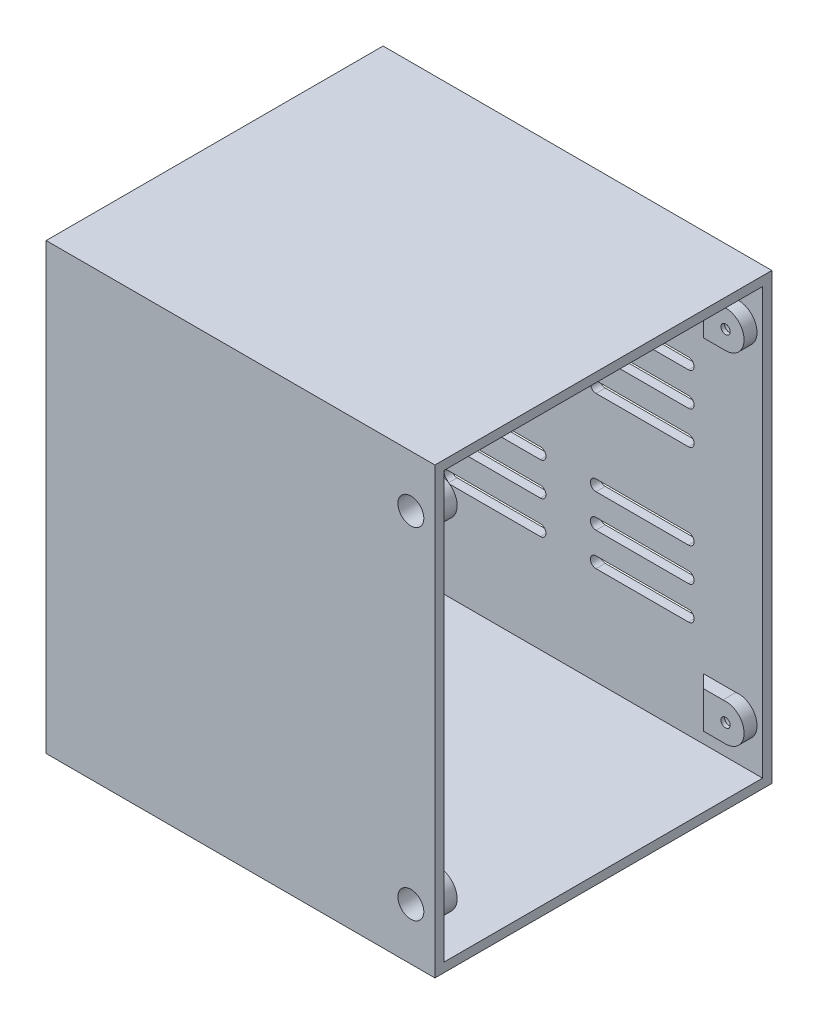
SolidWorks part; units mm, degrees
ref_plane "Front Plane" through (0, 0, 0) normal (0, 0, 1) x (1, 0, 0)
ref_plane "Top Plane" through (0, 0, 0) normal (0, 1, 0) x (1, 0, 0)
ref_plane "Right Plane" through (0, 0, 0) normal (1, 0, 0) x (0, 0, -1)
sketch "Sketch1" plane through (205.5525, 0, 0) normal (1, 0, 0) x (0, 0, -1)
  line L0 (1.5129, 48.8646) -> (1.513, -71.1354) construction
  line L1 (-89.4871, 48.8644) -> (1.5129, 48.8646) construction
  line L2 (-89.4871, 48.8644) -> (-89.487, -71.1356) construction
  line L3 (-89.487, -71.1356) -> (1.513, -71.1354) construction
  line L4 (1.5129, 48.8646) -> (1.513, -71.1354)
  line L5 (-89.4871, 48.8644) -> (1.5129, 48.8646)
  line L6 (-89.4871, 48.8644) -> (-89.487, -71.1356)
  line L7 (-89.487, -71.1356) -> (1.513, -71.1354)
  line L8 (-86.987, -68.6356) -> (-0.987, -68.6355)
  line L9 (-0.9871, 46.3645) -> (-0.987, -68.6355)
  line L10 (-86.9871, 46.3644) -> (-0.9871, 46.3645)
  line L11 (-86.9871, 46.3644) -> (-86.987, -68.6356)
  dimension "D1" = 2.5
extrude "Boss-Extrude1" add sketch "Sketch1" along normal up to surface (105 mm away)
sketch "Sketch2" plane through (0, 0, 86.9871) normal (0, 0, -1) x (-1, 0, 0)
  line L0 (-205.5525, 46.3645) -> (-205.5525, -68.6355) construction
  line L1 (-208.4525, -46.1353) -> (-206.5525, -46.1353)
  line L2 (-208.4525, -46.1353) -> (-208.4525, -40.1355)
  line L3 (-208.4525, -40.1355) -> (-206.5525, -40.1355)
  line L4 (-206.5525, -46.1353) -> (-206.5525, -40.1355)
  line L5 (-206.5525, 23.8645) -> (-208.4525, 23.8645)
  line L6 (-206.5525, 23.8645) -> (-206.5525, 17.8647)
  line L7 (-206.5525, 17.8647) -> (-208.4525, 17.8647)
  line L8 (-208.4525, 23.8645) -> (-208.4525, 17.8647)
  dimension "D1" = 0.1
  dimension "D2" = 1
  dimension "D3" = 0.1
  dimension "D4" = 1
  dimension "D5" = 0
  dimension "D6" = 0
  dimension "D7" = 0
  dimension "D8" = 0
extrude "Boss-Extrude2" add sketch "Sketch2" along normal offset from surface (1.3 mm away) 0.2
sketch "Sketch3" plane through (0, 0, 0.9871) normal (0, 0, 1) x (1, 0, 0)
  line L1 (210.0525, 28.8645) -> (225.0525, 28.8645)
  line L2 (210.0525, 28.8645) -> (210.0525, -51.1355)
  line L3 (210.0525, -51.1355) -> (225.0525, -51.1355)
  line L4 (225.0525, 28.8645) -> (225.0525, -51.1355)
  line L6 (205.5525, -68.6355) -> (205.5525, 46.3645) construction
  line L7 (310.5525, -71.1355) -> (205.5525, -71.1355) construction
  line L8 (310.5525, 48.8645) -> (205.5525, 48.8645) construction
  dimension "D1" = 4.5
  dimension "D2" = 15
  dimension "D3" = 20
  dimension "D4" = 20
extrude "Cut-Extrude1" cut sketch "Sketch3" against normal blind 0.5
sketch "Sketch4" plane through (0, 0, 0.9871) normal (0, 0, 1) x (1, 0, 0)
  line L0 (212.0525, 39.8645) -> (205.5525, 39.8645)
  line L1 (205.5525, -68.6355) -> (205.5525, 46.3645) construction
  line L2 (212.0525, 29.8645) -> (205.5525, 29.8645)
  line L3 (205.5525, 29.8645) -> (205.5525, 39.8645)
  line L4 (212.0525, -52.1355) -> (205.5525, -52.1355)
  line L5 (212.0525, -62.1355) -> (205.5525, -62.1355)
  line L6 (205.5525, -62.1355) -> (205.5525, -52.1355)
  line L7 (304.0525, -62.1355) -> (294.0525, -62.1355)
  line L8 (294.0525, -62.1355) -> (294.0525, -52.1855)
  line L9 (304.1025, -52.1855) -> (294.0525, -52.1855)
  line L10 (304.0525, 29.8645) -> (294.0525, 29.8645)
  line L11 (304.0525, 39.8645) -> (294.0525, 39.8645)
  line L12 (294.0525, 39.8645) -> (294.0525, 29.8645)
  circle A0 centre (212.0525, 34.8645) radius 2.25 construction
  circle A1 centre (212.0525, -57.1355) radius 2.25 construction
  circle A2 centre (212.0525, 34.8645) radius 2.25 construction
  circle A3 centre (212.0525, -57.1355) radius 2.25 construction
  circle A4 centre (212.0525, -57.1355) radius 5
  circle A5 centre (212.0525, 34.8645) radius 5
  circle A6 centre (212.0525, -57.1355) radius 3.5
  circle A7 centre (212.0525, 34.8645) radius 3.5
  circle A8 centre (212.0525, 34.8645) radius 1.25
  circle A9 centre (212.0525, -57.1355) radius 1.25
  circle A10 centre (304.0525, 34.8645) radius 1.6 construction
  circle A11 centre (304.0525, -57.1355) radius 1.6 construction
  circle A12 centre (304.0525, 34.8645) radius 1.6 construction
  circle A13 centre (304.0525, -57.1355) radius 1.6 construction
  circle A14 centre (304.0525, 34.8645) radius 5
  circle A15 centre (304.0525, -57.1355) radius 5
  circle A16 centre (304.0525, -57.1355) radius 3.5
  circle A17 centre (304.0525, -57.1355) radius 1.25
  circle A18 centre (304.0525, 34.8645) radius 3.5
  circle A19 centre (304.0525, 34.8645) radius 1.25
  line M7 (205.5525, 46.3645) -> (205.5525, -68.6355)
  dimension "D1" = 10
  dimension "D2" = 10
  dimension "D3" = 7
  dimension "D4" = 7
  dimension "D5" = 2.5
  dimension "D6" = 2.5
  dimension "D7" = 10
  dimension "D8" = 7
  dimension "D9" = 2.5
  dimension "D10" = 10
  dimension "D11" = 7
  dimension "D12" = 2.5
  dimension "D13" = 10
  dimension "D14" = 10
extrude "Boss-Extrude3" add sketch "Sketch4" along normal up to surface (3.5 mm away) contours A5 A7 | A4 A6 | A5 L0 L2 M7 | A4 L4 L5 M7 | A15 A16 | A14 A18 | A14 L11 L12 L10 | A15 L9 L8 L7 region at (206.9332, 34.8645, 0.9871) region at (208.8025, -52.2547, 0.9871) region at (215.488, 38.3001, 0.9871) region at (215.488, -53.6999, 0.9871) region at (299.2061, -57.479, 0.9871) region at (297.1787, -57.1748, 0.9871) region at (297.1915, 34.8645, 0.9871) region at (299.1939, 34.8645, 0.9871)
extrude "Boss-Extrude4" add sketch "Sketch4<3>" against normal blind 1 from surface contours A7 A8 | A18 A19 | A16 A17 | A6 A9 region at (208.6515, -57.1355, 0.9871) region at (208.6515, 34.8645, 0.9871) region at (300.6515, -57.1355, 0.9871) region at (300.6515, 34.8645, 0.9871) starting at face at (307.5525, 34.8645, 4.4871)
sketch "Sketch4<3>" plane through (0, 0, 0.9871) normal (0, 0, 1) x (1, 0, 0) same geometry as "Sketch4"
extrude "Cut-Extrude2" cut sketch "Sketch4<4>" against normal through all contours A6 A9 | A9 | A7 A8 | A8 | A17 | A16 A17 | A19 | A18 A19 region at (208.6515, -57.1355, 0.9871) region at (208.6515, 34.8645, 0.9871) region at (212.0525, 34.8645, 0.9871) region at (212.0525, -57.1355, 0.9871) region at (300.6515, -57.1355, 0.9871) region at (304.0525, -57.1355, 0.9871) region at (300.6515, 34.8645, 0.9871) region at (304.0525, 34.8645, 0.9871)
sketch "Sketch4<4>" plane through (0, 0, 0.9871) normal (0, 0, 1) x (1, 0, 0) same geometry as "Sketch4"
chamfer "Chamfer1" distance 4 angle 45 1 edges at (294.0525, -57.1605, 4.4871)
chamfer "Chamfer2" distance 4 angle 45 1 edges at (294.0525, 34.8645, 4.4871)
sketch "Sketch5" plane through (0, 0, -1.5129) normal (0, 0, -1) x (-1, 0, 0)
  line L0 (-258.0525, 48.8645) -> (-258.0525, -71.1355) construction
  line L1 (-310.5525, 48.8645) -> (-205.5525, 48.8645) construction
  line L2 (-310.5525, -71.1355) -> (-205.5525, -71.1355) construction
  line L3 (-310.5525, -11.1355) -> (-205.5525, -11.1355) construction
  line L4 (-310.5525, -71.1355) -> (-310.5525, 48.8645) construction
  line L5 (-205.5525, 48.8645) -> (-205.5525, -71.1355) construction
  line L6 (-290.5525, 10.8645) -> (-290.5525, 7.8645)
  line L7 (-290.5525, 1.8645) -> (-265.5525, 1.8645)
  line L8 (-290.5525, 1.8645) -> (-290.5525, -1.1355)
  line L9 (-290.5525, -1.1355) -> (-265.5525, -1.1355)
  line L10 (-265.5525, 1.8645) -> (-265.5525, -1.1355)
  line L11 (-290.5525, 10.8645) -> (-265.5525, 10.8645)
  line L12 (-265.5525, 10.8645) -> (-265.5525, 7.8645)
  line L13 (-290.5525, 7.8645) -> (-265.5525, 7.8645)
  line L14 (-290.5525, 19.8645) -> (-290.5525, 16.8645)
  line L15 (-290.5525, 19.8645) -> (-265.5525, 19.8645)
  line L16 (-265.5525, 19.8645) -> (-265.5525, 16.8645)
  line L17 (-290.5525, 16.8645) -> (-265.5525, 16.8645)
  line L18 (-225.5525, 16.8645) -> (-250.5525, 16.8645)
  line L19 (-250.5525, 19.8645) -> (-250.5525, 16.8645)
  line L20 (-225.5525, 19.8645) -> (-250.5525, 19.8645)
  line L21 (-225.5525, 19.8645) -> (-225.5525, 16.8645)
  line L22 (-225.5525, 7.8645) -> (-250.5525, 7.8645)
  line L23 (-250.5525, 10.8645) -> (-250.5525, 7.8645)
  line L24 (-225.5525, 10.8645) -> (-250.5525, 10.8645)
  line L25 (-250.5525, 1.8645) -> (-250.5525, -1.1355)
  line L26 (-225.5525, -1.1355) -> (-250.5525, -1.1355)
  line L27 (-225.5525, 1.8645) -> (-225.5525, -1.1355)
  line L28 (-225.5525, 1.8645) -> (-250.5525, 1.8645)
  line L29 (-225.5525, 10.8645) -> (-225.5525, 7.8645)
  line L30 (-225.5525, -33.1355) -> (-225.5525, -30.1355)
  line L31 (-225.5525, -24.1355) -> (-250.5525, -24.1355)
  line L32 (-225.5525, -24.1355) -> (-225.5525, -21.1355)
  line L33 (-225.5525, -21.1355) -> (-250.5525, -21.1355)
  line L34 (-250.5525, -24.1355) -> (-250.5525, -21.1355)
  line L35 (-225.5525, -33.1355) -> (-250.5525, -33.1355)
  line L36 (-250.5525, -33.1355) -> (-250.5525, -30.1355)
  line L37 (-225.5525, -30.1355) -> (-250.5525, -30.1355)
  line L38 (-225.5525, -42.1355) -> (-225.5525, -39.1355)
  line L39 (-225.5525, -42.1355) -> (-250.5525, -42.1355)
  line L40 (-250.5525, -42.1355) -> (-250.5525, -39.1355)
  line L41 (-225.5525, -39.1355) -> (-250.5525, -39.1355)
  line L42 (-290.5525, -39.1355) -> (-265.5525, -39.1355)
  line L43 (-265.5525, -42.1355) -> (-265.5525, -39.1355)
  line L44 (-290.5525, -42.1355) -> (-265.5525, -42.1355)
  line L45 (-290.5525, -42.1355) -> (-290.5525, -39.1355)
  line L46 (-290.5525, -30.1355) -> (-265.5525, -30.1355)
  line L47 (-265.5525, -33.1355) -> (-265.5525, -30.1355)
  line L48 (-290.5525, -33.1355) -> (-265.5525, -33.1355)
  line L49 (-265.5525, -24.1355) -> (-265.5525, -21.1355)
  line L50 (-290.5525, -21.1355) -> (-265.5525, -21.1355)
  line L51 (-290.5525, -24.1355) -> (-290.5525, -21.1355)
  line L52 (-290.5525, -24.1355) -> (-265.5525, -24.1355)
  line L53 (-290.5525, -33.1355) -> (-290.5525, -30.1355)
  arc A0 (-265.5525, 1.8645) -> (-265.5525, -1.1355) centre (-265.5525, 0.3645) cw
  arc A1 (-290.5525, -1.1355) -> (-290.5525, 1.8645) centre (-290.5525, 0.3645) cw
  arc A2 (-265.5525, 10.8645) -> (-265.5525, 7.8645) centre (-265.5525, 9.3645) cw
  arc A3 (-290.5525, 7.8645) -> (-290.5525, 10.8645) centre (-290.5525, 9.3645) cw
  arc A4 (-265.5525, 19.8645) -> (-265.5525, 16.8645) centre (-265.5525, 18.3645) cw
  arc A5 (-290.5525, 16.8645) -> (-290.5525, 19.8645) centre (-290.5525, 18.3645) cw
  arc A6 (-225.5525, 16.8645) -> (-225.5525, 19.8645) centre (-225.5525, 18.3645) ccw
  arc A7 (-250.5525, 19.8645) -> (-250.5525, 16.8645) centre (-250.5525, 18.3645) ccw
  arc A8 (-225.5525, 7.8645) -> (-225.5525, 10.8645) centre (-225.5525, 9.3645) ccw
  arc A9 (-250.5525, 10.8645) -> (-250.5525, 7.8645) centre (-250.5525, 9.3645) ccw
  arc A10 (-225.5525, -1.1355) -> (-225.5525, 1.8645) centre (-225.5525, 0.3645) ccw
  arc A11 (-250.5525, 1.8645) -> (-250.5525, -1.1355) centre (-250.5525, 0.3645) ccw
  arc A12 (-250.5525, -24.1355) -> (-250.5525, -21.1355) centre (-250.5525, -22.6355) cw
  arc A13 (-225.5525, -21.1355) -> (-225.5525, -24.1355) centre (-225.5525, -22.6355) cw
  arc A14 (-250.5525, -33.1355) -> (-250.5525, -30.1355) centre (-250.5525, -31.6355) cw
  arc A15 (-225.5525, -30.1355) -> (-225.5525, -33.1355) centre (-225.5525, -31.6355) cw
  arc A16 (-250.5525, -42.1355) -> (-250.5525, -39.1355) centre (-250.5525, -40.6355) cw
  arc A17 (-225.5525, -39.1355) -> (-225.5525, -42.1355) centre (-225.5525, -40.6355) cw
  arc A18 (-290.5525, -39.1355) -> (-290.5525, -42.1355) centre (-290.5525, -40.6355) ccw
  arc A19 (-265.5525, -42.1355) -> (-265.5525, -39.1355) centre (-265.5525, -40.6355) ccw
  arc A20 (-290.5525, -30.1355) -> (-290.5525, -33.1355) centre (-290.5525, -31.6355) ccw
  arc A21 (-265.5525, -33.1355) -> (-265.5525, -30.1355) centre (-265.5525, -31.6355) ccw
  arc A22 (-290.5525, -21.1355) -> (-290.5525, -24.1355) centre (-290.5525, -22.6355) ccw
  arc A23 (-265.5525, -24.1355) -> (-265.5525, -21.1355) centre (-265.5525, -22.6355) ccw
  dimension "D1" = 3
  dimension "D2" = 25
  dimension "D3" = 10
  dimension "D4" = 7.5
  dimension "D6" = 6
  dimension "D5" = 3
extrude "Cut-Extrude3" cut sketch "Sketch5" against normal blind 3 contours L14 L17 L16 L15 | A5 L14 | A4 L16 | A1 L8 | L10 L7 L8 L9 | A0 L10 | A2 L12 | L6 L13 L12 L11 | A3 L6 | A17 L38 | L38 L41 L40 L39 | A16 L40 | A14 L36 | L30 L37 L36 L35 | A15 L30 | A13 L32 | L34 L31 L32 L33 | A12 L34 | L51 A22 | L51 L52 L49 L50 | L49 A23 | L47 A21 | L53 L48 L47 L46 | L53 A20 | L45 A18 | L45 L44 L43 L42 | L43 A19 | L21 A6 | L21 L20 L19 L18 | L19 A7 | L23 A9 | L29 L24 L23 L22 | L29 A8 | L27 A10 | L27 L28 L25 L26 | L25 A11 region at (278.0525, 9.3645, -1.5129) region at (291.1891, 9.3645, -1.5129) region at (264.9159, 9.3645, -1.5129) region at (278.0525, 0.3645, -1.5129) region at (291.1891, 0.3645, -1.5129) region at (264.9159, 0.3645, -1.5129) region at (278.0525, 18.3645, -1.5129) region at (291.1891, 18.3645, -1.5129) region at (264.9159, 18.3645, -1.5129) region at (238.0525, 18.3645, -1.5129) region at (224.9159, 18.3645, -1.5129) region at (251.1891, 18.3645, -1.5129) region at (238.0525, 9.3645, -1.5129) region at (224.9159, 9.3645, -1.5129) region at (251.1891, 9.3645, -1.5129) region at (238.0525, 0.3645, -1.5129) region at (251.1891, 0.3645, -1.5129) region at (224.9159, 0.3645, -1.5129) region at (238.0525, -31.6355, -1.5129) region at (224.9159, -31.6355, -1.5129) region at (251.1891, -31.6355, -1.5129) region at (238.0525, -22.6355, -1.5129) region at (224.9159, -22.6355, -1.5129) region at (251.1891, -22.6355, -1.5129) region at (238.0525, -40.6355, -1.5129) region at (224.9159, -40.6355, -1.5129) region at (251.1891, -40.6355, -1.5129) region at (278.0525, -40.6355, -1.5129) region at (291.1891, -40.6355, -1.5129) region at (264.9159, -40.6355, -1.5129) region at (278.0525, -31.6355, -1.5129) region at (291.1891, -31.6355, -1.5129) region at (264.9159, -31.6355, -1.5129) region at (278.0525, -22.6355, -1.5129) region at (264.9159, -22.6355, -1.5129) region at (291.1891, -22.6355, -1.5129)
extrude "Boss-Extrude5" add sketch "Sketch4<6>" against normal up to surface (5 mm away) from surface contours A15 L9 L8 L7 | A15 A16 | A14 L11 L12 L10 | A14 A18 region at (299.2061, -57.479, 0.9871) region at (297.1787, -57.1748, 0.9871) region at (297.1915, 34.8645, 0.9871) region at (299.1939, 34.8645, 0.9871) starting at face at (258.0525, -11.1355, 86.9871)
sketch "Sketch4<6>" plane through (0, 0, 0.9871) normal (0, 0, 1) x (1, 0, 0) same geometry as "Sketch4"
extrude "Boss-Extrude6" add sketch "Sketch4<7>" along normal blind 1 from surface contours A14 A18 | A18 A19 | A16 A17 | A15 A16 region at (299.2061, -57.479, 0.9871) region at (299.1939, 34.8645, 0.9871) region at (300.6515, -57.1355, 0.9871) region at (300.6515, 34.8645, 0.9871) starting at face at (300.3025, 34.8645, 81.9871)
sketch "Sketch4<7>" plane through (0, 0, 0.9871) normal (0, 0, 1) x (1, 0, 0) same geometry as "Sketch4"
extrude "Cut-Extrude4" cut sketch "Sketch4<8>" along normal through all from surface contours A16 A17 | A18 A19 | A17 | A19 region at (300.6515, -57.1355, 0.9871) region at (304.0525, -57.1355, 0.9871) region at (300.6515, 34.8645, 0.9871) region at (304.0525, 34.8645, 0.9871) starting at face at (300.2112, -57.0658, 86.9871)
sketch "Sketch4<8>" plane through (0, 0, 0.9871) normal (0, 0, 1) x (1, 0, 0) same geometry as "Sketch4"
chamfer "Chamfer3" distance 5 angle 45 1 edges at (294.0525, -57.1605, 81.9871)
chamfer "Chamfer4" distance 5 angle 45 1 edges at (294.0525, 34.8645, 81.9871)
equation "\"R\"=9.03994"
equation "\"R_MOUNT_OUTER\"=10"
equation "\"D1@Sketch4\"=\"R_MOUNT_OUTER\""
equation "\"D2@Sketch4\"=\"R_MOUNT_OUTER\""
equation "\"R_MOUNT_INNER\"=7"
equation "\"D3@Sketch4\"=\"R_MOUNT_INNER\""
equation "\"D4@Sketch4\"=\"R_MOUNT_INNER\""
equation "\"R_SCREW\"=2.5"
equation "\"D5@Sketch4\"=\"R_SCREW\""
equation "\"D6@Sketch4\"=\"R_SCREW\""
equation "\"D7@Sketch4\"=\"R_MOUNT_OUTER\""
equation "\"D8@Sketch4\"=\"R_MOUNT_INNER\""
equation "\"D9@Sketch4\"=\"R_SCREW\""
equation "\"D10@Sketch4\"=\"R_MOUNT_OUTER\""
equation "\"D11@Sketch4\"=\"R_MOUNT_INNER\""
equation "\"D12@Sketch4\"=\"R_SCREW\""
